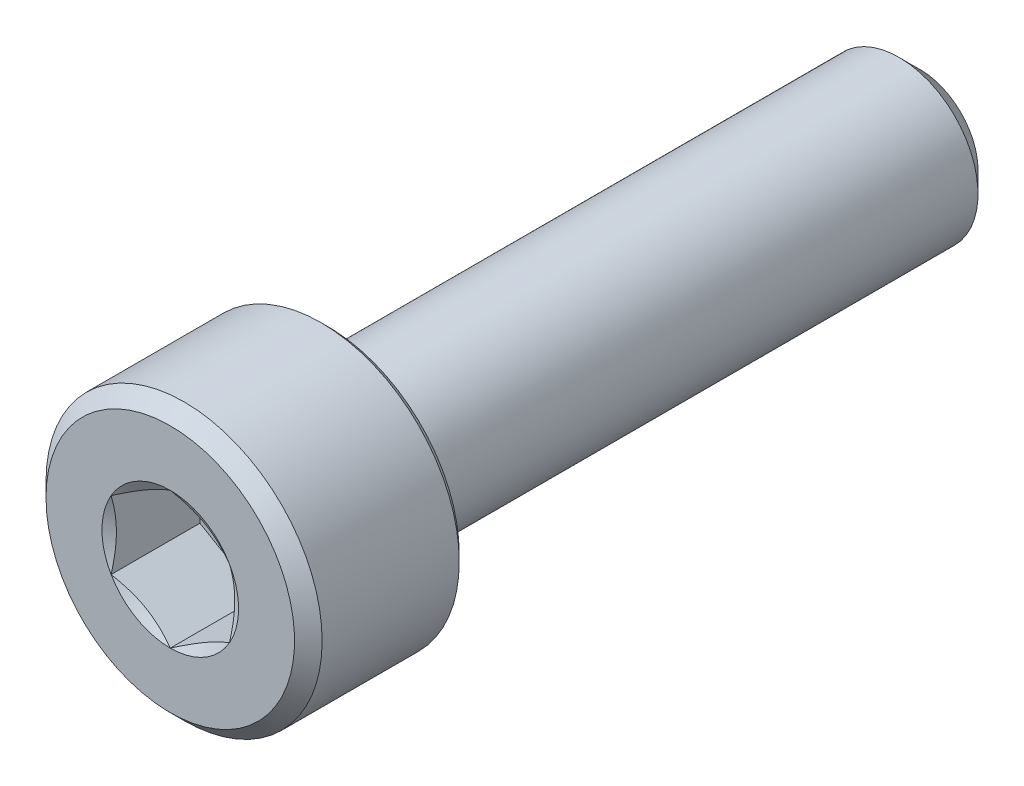
SolidWorks part; units mm, degrees
ref_plane "Front Plane" through (0, 0, 0) normal (0, 0, 1) x (1, 0, 0)
ref_plane "Top Plane" through (0, 0, 0) normal (0, 1, 0) x (1, 0, 0)
ref_plane "Right Plane" through (0, 0, 0) normal (1, 0, 0) x (0, 0, -1)
sketch "Sketch1" plane through (0, 0, 0) normal (1, 0, 0) x (0, 0, -1)
  line L0 (9.5, 0) -> (-9.5, 0) construction
  line L1 (-9.5, 0) -> (-9.5, 3.5) construction
  line L2 (-5.5, 2) -> (-5.5, 0) construction
  line L3 (8.8, 0) -> (8.8, 0.7) construction
  line L4 (-5.5, 0) -> (-5.5, -2) construction
  point P6 (-9.5, -1.5)
  point P9 (-9.5, 1.5)
  point P10 (7.75, -2)
  dimension "D1" = 0.7
  dimension "D2" = 1.75
sketch "Sketch2" plane through (0, 0, 0) normal (1, 0, 0) x (0, 0, -1)
  line L0 (9.5, 1.475) -> (8.975, 2)
  line L1 (-9.5, 3.5) -> (-5.5, 3.5)
  line L2 (-9.5, 3.5) -> (-9.5, 0)
  line L4 (-5.5, 3.5) -> (-5.5, 2)
  line L5 (-5.5, 2) -> (8.975, 2)
  line L8 (9.5, 1.475) -> (9.5, 0)
  line L9 (9.5, 0) -> (-9.5, 0) construction
  line L10 (9.5, 0) -> (-9.5, 0)
  dimension "D1" = 135
  dimension "D2" = 0.525
revolve "Revolve1" add sketch "Sketch2" angle 360 about L10
sketch "Sketch4" plane through (0, 0, 9.5) normal (0, 0, 1) x (1, 0, 0)
  line L1 (0, 1.7321) -> (-1.5, 0.866)
  line L2 (-1.5, 0.866) -> (-1.5, -0.866)
  line L3 (-1.5, -0.866) -> (0, -1.7321)
  line L4 (0, -1.7321) -> (1.5, -0.866)
  line L5 (1.5, -0.866) -> (1.5, 0.866)
  line L6 (1.5, 0.866) -> (0, 1.7321)
  circle A0 centre (0, 0) radius 1.5 construction
  circle A1 centre (0, 0) radius 3.5 construction
  circle A2 centre (0, 0) radius 3.5 construction
  dimension "D1" = 3
extrude "Cut-Extrude1" cut sketch "Sketch4" against normal blind 2.25
sketch "Sketch5" plane through (0, 0, 9.5) normal (0, 0, 1) x (1, 0, 0)
  circle A0 centre (0, 0) radius 1.7321
extrude "Cut-Extrude2" cut sketch "Sketch5" against normal blind 10 draft 60
chamfer "Chamfer1" distance 0.35 angle 45 1 edges at (-3.5, 0, 9.5)
chamfer "Chamfer2" distance 0.175 angle 45 1 edges at (-3.5, 0, 5.5)
sketch "Sketch3" [suppressed] plane through (0, 0, -9.5) normal (0, 0, -1) x (-1, 0, 0)
  circle A0 centre (0, 0) radius 2 construction
  circle A1 centre (0, 0) radius 2
curve "Helix/Spiral1" [suppressed] pitch 0.7 height 15.35 turns 21.9286
sketch "Sketch7" [suppressed] plane through (0, 0, 0) normal (1, 0, 0) x (0, 0, -1)
  line L0 (9.4562, 2.0758) -> (9.8062, 1.4696) construction
  line L1 (9.8062, 1.4696) -> (10.1562, 2.0758) construction
  line L2 (10.1562, 2.0758) -> (9.4562, 2.0758) construction
  line L3 (9.5, 2) -> (10.1125, 2)
  line L4 (9.8062, 2.0758) -> (9.8062, 2) construction
  line L5 (9.8062, 2) -> (9.8062, 1.5453) construction
  line L6 (9.8062, 1.5453) -> (9.8062, 1.4696) construction
  line L7 (9.7625, 1.5453) -> (9.85, 1.5453)
  line L8 (9.4781, 2.0379) -> (10.1344, 2.0379) construction
  line L9 (9.85, 1.5453) -> (10.1125, 2)
  line L10 (9.7625, 1.5453) -> (9.5, 2)
  point P0 (9.8062, 2.0379)
  dimension "D1" = 0.7
  dimension "D2" = 0.0875
sweep "Cut-Sweep1" [suppressed] cut profiles "Sketch7" path "Helix/Spiral1"
sketch "Sketch8" [suppressed] plane through (0, 0, 0) normal (1, 0, 0) x (0, 0, -1)
  line L0 (-7.25, 0) -> (-7.25, 2.0379)
  line L1 (-7.25, -0.866) -> (-7.25, 0.866) construction
  line L2 (-7.25, 2.0379) -> (-5.15, 2.0379)
  line L3 (-5.15, 2.0379) -> (-3.9734, 0)
  line L4 (-3.9734, 0) -> (-7.25, 0)
  line L5 (9.5, 0) -> (-9.5, 0) construction
  line L6 (-5.5, -3.325) -> (-5.5, 3.325) construction
  line L9 (9.4781, 2.0379) -> (10.1344, 2.0379) construction
  dimension "D1" = 60
  dimension "D2" = 0.35
revolve "Revolve2" [suppressed] add sketch "Sketch8" angle 360 about L4
equation "\"D1@Sketch1\" = \"Thread Pitch@Sketch1\""
equation "\"D2@Sketch2\"=\"D1@Sketch1\"*.75"
equation "\"D4@Helix/Spiral1\" = \"Thread Pitch@Sketch1\""
equation "\"D3@Helix/Spiral1\"=\"Length@Sketch1\" + (\"Thread Pitch@Sketch1\"*0.5)"
equation "\"D1@Sketch4\"=\"drive Size@Sketch1\""
equation "\"D1@Cut-Extrude1\"=\"D1@Sketch4\"*.75"
equation "\"D19\"= \"D1@Sketch4\" * .75"
equation "\"D1@Chamfer1\" = \"Head Diameter@Sketch1\" * .05"
equation "\"D1@Chamfer2\"=\"D1@Chamfer1\"/2"
equation "\"D2@Sketch7\"=\"D1@Sketch7\"/8"
equation "\"D1@Sketch7\"=\"D4@Helix/Spiral1\""
equation "\"D2@Sketch1\" = \"Thread Pitch@Sketch1\" * 2.5"
equation "\"D2@Sketch8\"=\"Thread Pitch@Sketch1\"*0.5"
